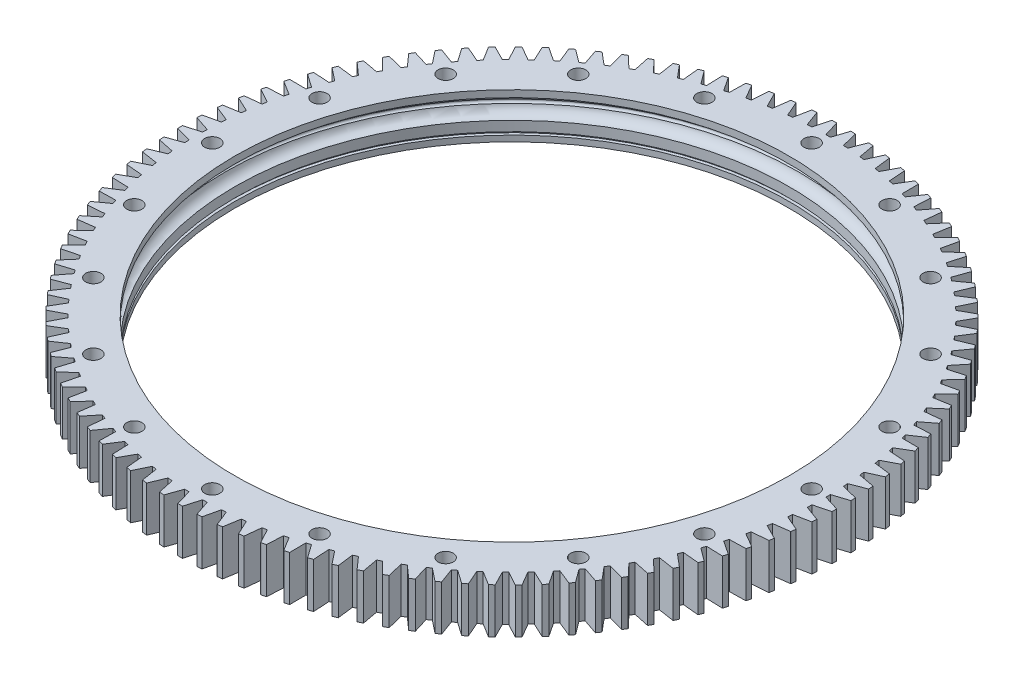
SolidWorks part; units mm, degrees
ref_plane "Plan de face" through (0, 0, 0) normal (0, 0, 1) x (1, 0, 0)
ref_plane "Plan de dessus" through (0, 0, 0) normal (0, 1, 0) x (1, 0, 0)
ref_plane "Plan de droite" through (0, 0, 0) normal (1, 0, 0) x (0, 0, -1)
sketch "Esquisse1" plane through (0, 0, 0) normal (0, 0, 1) x (1, 0, 0)
  line L0 (0, 0) -> (-335.4, 0) construction
  line L1 (-335.4, 0) -> (-335.4, 46) construction
  line L2 (-335.4, 46) -> (0, 46) construction
  line L3 (0, 46) -> (0, 0) construction
  line L4 (-335.4, 0) -> (-282, 0) construction
  line L5 (-282, 0) -> (-282, 10) construction
  line L6 (-282, 10) -> (-282, 30) construction
  line L7 (-282, 46) -> (-282, 42.7532) construction
  line L8 (-282, 46) -> (-335.4, 46) construction
  line L9 (-282, 20) -> (-291.5, 20) construction
  line L10 (-291.5, 20) -> (-293.5, 20) construction
  line L11 (-280, 46) -> (-280, 40) construction
  line L12 (-280, 40) -> (-277, 40) construction
  line L13 (-277, 40) -> (-277, 37) construction
  line L14 (-282, 46) -> (-282, 30) construction
  line L15 (-282, 42.7532) -> (-282, 46) construction
  line L16 (-281, 46) -> (-281, 0) construction
  line L17 (-280, 30) -> (-280, 46) construction
  line L18 (-280, 46) -> (-239.5, 46) construction
  line L19 (-239.5, 46) -> (-239.5, 0) construction
  line L20 (-239.5, 0) -> (-280, 0) construction
  line L21 (-277, 37) -> (-280, 37) construction
  line L22 (-280, 37) -> (-280, 30) construction
  line L23 (-280, 0) -> (-280, 10) construction
  line L24 (-280, 37) -> (-282, 37) construction
  line L25 (-282, 37) -> (-335.4, 37) construction
  line L26 (-335.4, 37) -> (-335.4, -9) construction
  line L27 (-282, 46) -> (-280, 46) construction
  line L28 (-335.4, -9) -> (-282, -9) construction
  line L29 (-282, 30) -> (-282, 37)
  line L30 (-282, 0) -> (-282, -3) construction
  line L31 (-282, -3) -> (-285, -3) construction
  line L32 (-285, -3) -> (-285, 0) construction
  line L33 (-285, 0) -> (-282, 0) construction
  line L34 (-282, 0) -> (-282, -9) construction
  line L35 (-282, 37) -> (-335.4, 37)
  line L36 (-335.4, 37) -> (-335.4, -9)
  line L37 (-335.4, -9) -> (-282, -9)
  line L38 (-282, -9) -> (-282, -3)
  line L39 (-282, -3) -> (-285, -3)
  line L40 (-285, -3) -> (-285, 0)
  line L41 (-285, 0) -> (-282, 0)
  line L42 (-282, 0) -> (-282, 10)
  arc A0 (-282, 30) -> (-282, 10) centre (-282, 20) ccw
  arc A1 (-291.8026, 21.977) -> (-291.8026, 18.023) centre (-291.5, 20) ccw
  arc A2 (-291.8026, 18.023) -> (-282, 10) centre (-282, 20) ccw construction
  arc A3 (-282, 30) -> (-291.8026, 21.977) centre (-282, 20) ccw construction
  arc A4 (-270.1974, 21.977) -> (-270.1974, 18.023) centre (-270.5, 20) cw construction
  arc A5 (-280, 30) -> (-280, 10) centre (-280, 20) cw construction
  arc A6 (-280, 30) -> (-270.1974, 21.977) centre (-280, 20) cw construction
  arc A7 (-270.1974, 18.023) -> (-280, 10) centre (-280, 20) cw construction
  dimension "D7" = 10
  dimension "D8" = 9.5
  dimension "D9" = 2
  dimension "D2" = 3
  dimension "D3" = 20
  dimension "D4" = 3
  dimension "D5" = 280
  dimension "D6" = 46
  dimension "D10" = 9
  dimension "D11" = 1
  dimension "D12" = 3
  dimension "D13" = 3
  dimension "D14" = 46
  dimension "D15" = 239.5
  dimension "D17" = 335.4
revolve "Révolution1" add sketch "Esquisse1" angle 360 about L3 region at (-310.3745, 13.6367, 0)
sketch "Esquisse4" plane through (0, 37, 0) normal (0, 1, 0) x (1, 0, 0)
  line L0 (0, 0) -> (-305, 0) construction
  circle A0 centre (-305, 0) radius 7.75
  point P38 (0, 0)
  dimension "D1" = 15.5
  dimension "D2" = 305
extrude "Enlèv. mat.-Extru.2" cut sketch "Esquisse4" against normal through all
ref_axis "Axe2" through (0, 45.15, 0) along (0, -1, 0)
pattern_circular "Répétition circulaire1" count 20 over 360 about axis through (0, 45.15, 0) along (0, -1, 0) of "Enlèv. mat.-Extru.2"
sketch "Esquisse5" plane through (0, 37, 0) normal (0, 1, 0) x (1, 0, 0)
  line L0 (0, 0) -> (-335.4, 0) construction
  line L1 (0, 0) -> (-334.8436, -19.3114) construction
  line L2 (-334.8436, -19.3114) -> (-387.2586, -22.3343)
  line L3 (-387.2586, -22.3343) -> (-387.2586, 0)
  line L4 (-387.2586, 0) -> (-335.4, 0)
  line L5 (-335.4, 0) -> (-335.3652, -4.8333)
  line L6 (-335.3652, -4.8333) -> (-319.3673, -9.2073)
  line L7 (-319.3673, -9.2073) -> (-319.2015, -13.8086)
  line L8 (-319.2015, -13.8086) -> (-334.8436, -19.3114)
  line L9 (-335.3652, -4.8333) -> (0, 0) construction
  line L10 (0, 0) -> (-319.3673, -9.2073) construction
  line L11 (-319.2015, -13.8086) -> (0, 0) construction
  circle A0 centre (0, 0) radius 335.4 construction
  circle A1 centre (0, 0) radius 335.4 construction
  circle A2 centre (0, 0) radius 319.5 construction
  dimension "D5" = 639
  dimension "D1" = 3.301
  dimension "D2" = 0.826
  dimension "D3" = 0.826
  dimension "D4" = 0.826
extrude "Enlèv. mat.-Extru.3" cut sketch "Esquisse5" against normal through all
pattern_circular "Répétition circulaire4" count 109 over 360 about axis through (0, 45.15, 0) along (0, -1, 0) of "Enlèv. mat.-Extru.3"
